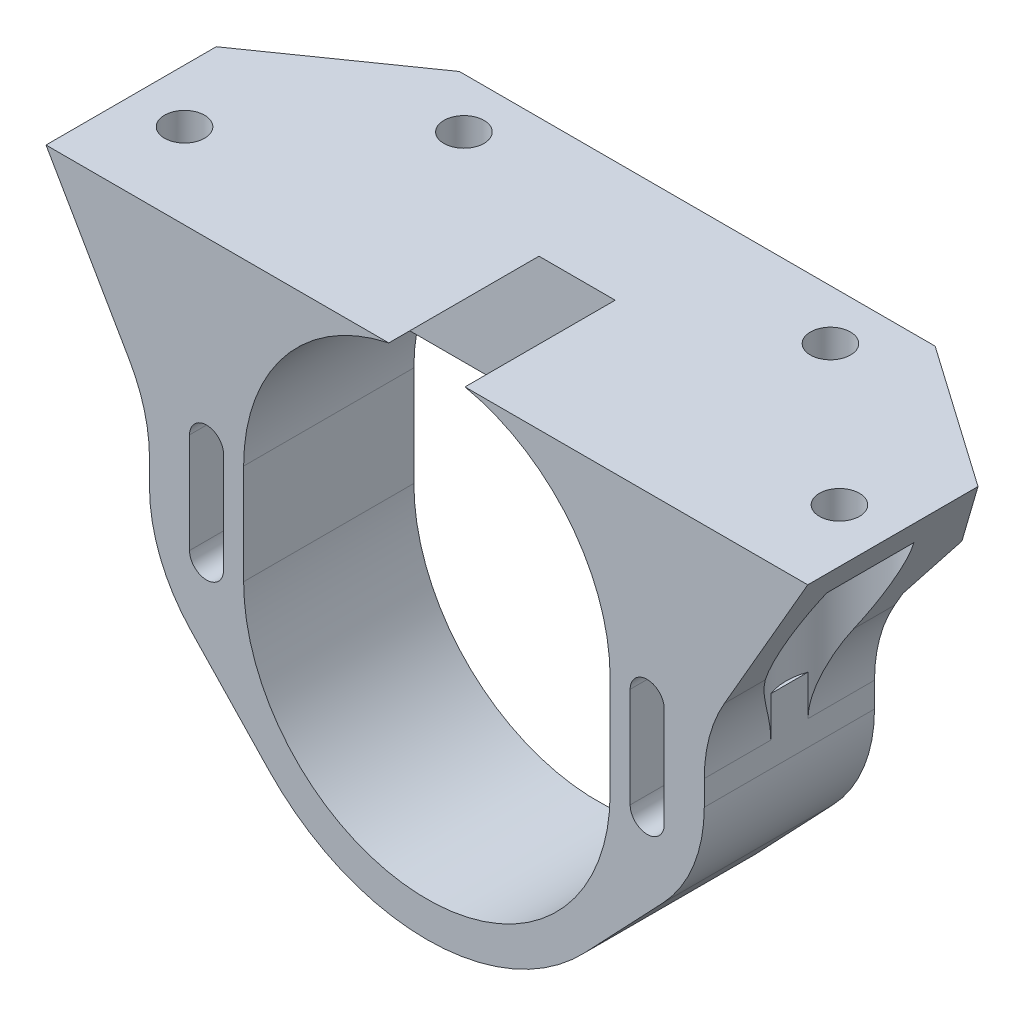
SolidWorks part; units mm, degrees
material "PA Type 6"
ref_plane "Front Plane" through (0, 0, 0) normal (0, 0, 1) x (1, 0, 0)
ref_plane "Top Plane" through (0, 0, 0) normal (0, 1, 0) x (1, 0, 0)
ref_plane "Right Plane" through (0, 0, 0) normal (1, 0, 0) x (0, 0, -1)
sketch "Sketch1" plane through (0, 0, 0) normal (0, 0, 1) x (1, 0, 0)
  line L0 (-18.3, -5) -> (-23.9501, -5) construction
  line L2 (150.8125, 17.9) -> (-150.8125, 17.9)
  line L3 (38.0346, 17.9) -> (3.8053, 17.9)
  line L4 (-15.8012, -25.0187) -> (-27.7, -12.5)
  line L5 (27.7, 0) -> (38.0346, 17.9)
  line L6 (18.3, 0) -> (18.3, -10)
  line L7 (18.3, -5) -> (23.9501, -5) construction
  line L8 (22, 0) -> (22, -10) construction
  line L9 (23.7, 0) -> (23.7, -10)
  line L10 (20.3, 0) -> (20.3, -10)
  line L11 (27.7, 0) -> (27.7, -12.5)
  line L12 (15.8012, -25.0187) -> (27.7, -12.5)
  line L13 (0, 0) -> (0, -39.0494) construction
  line L14 (-27.7, 0) -> (-27.7, -12.5)
  line L15 (-18.3, 0) -> (-18.3, -10)
  line L16 (-27.7, 0) -> (-38.0346, 17.9)
  line L17 (-38.0346, 17.9) -> (-3.8053, 17.9)
  line L18 (-22, 0) -> (-22, -10) construction
  line L19 (-23.7, 0) -> (-23.7, -10)
  line L20 (-20.3, 0) -> (-20.3, -10)
  arc A0 (18.3, 0) -> (3.8053, 17.9) centre (0, 0) ccw
  circle A1 centre (0, 0) radius 18
  circle A2 centre (0, 0) radius 18 construction
  circle A3 centre (0, 0) radius 18.3 construction
  arc A5 (-18.3, 0) -> (-3.8053, 17.9) centre (0, 0) cw
  arc A6 (18.3, -10) -> (-18.3, -10) centre (0, -10) cw
  arc A7 (15.8012, -25.0187) -> (-15.8012, -25.0187) centre (0, -10) cw
  arc A8 (21.8, -10) -> (4.533, -31.3235) centre (0, -10) cw construction
  arc A9 (23.7, 0) -> (20.3, 0) centre (22, 0) ccw
  arc A10 (20.3, -10) -> (23.7, -10) centre (22, -10) ccw
  arc A11 (18.3, -10) -> (3.8053, -27.9) centre (0, -10) cw construction
  arc A12 (-23.7, 0) -> (-20.3, 0) centre (-22, 0) cw
  arc A13 (-20.3, -10) -> (-23.7, -10) centre (-22, -10) cw
  point P19 (22, -5)
  point P41 (-22, -5)
  dimension "D7" = 1.7
  dimension "D4" = 60
  dimension "D5" = 10
  dimension "D8" = 4
  dimension "D9" = 2.5
  dimension "D10" = 10
  dimension "D1" = 0
  dimension "D2" = 0.3
  dimension "D3" = 0.1
  dimension "D6" = 3.5
extrude "Boss-Extrude1" add sketch "Sketch1" along normal offset from surface (17 mm away) 2.5 offset beyond the face yes
sketch "Sketch2" plane through (0, 0, 17) normal (0, 0, 1) x (1, 0, 0)
  line L0 (38.0346, 17.9) -> (-38.0346, 17.9)
  line L1 (-38.0346, 17.9) -> (-30.5868, 5)
  line L2 (-38.0346, 17.9) -> (-27.7, 0) construction
  line L3 (-30.5868, 5) -> (30.5868, 5)
  line L4 (27.7, 0) -> (38.0346, 17.9) construction
  line L5 (30.5868, 5) -> (38.0346, 17.9)
  dimension "D1" = 5
extrude "Boss-Extrude2" add sketch "Sketch2" along normal blind 2 from surface starting at face at (22, -5, 0)
sketch "Sketch3" plane through (0, 0, 0) normal (0, 1, 0) x (1, 0, 0)
  line L0 (38.0346, -17) -> (38.0346, 0) construction
  line L1 (27.7, -17) -> (27.7, 0) construction
  circle A0 centre (32.7, -8.5) radius 2
  point P6 (38.0346, -8.5)
  dimension "D1" = 4
  dimension "D2" = 5
extrude "Cut-Extrude2" cut sketch "Sketch3" along normal through all
sketch "Sketch4" plane through (0, 0, 0) normal (0, 1, 0) x (1, 0, 0)
  line L0 (38.0346, -17) -> (38.0346, 0) construction
  circle A0 centre (32.7, -8.5) radius 5.3346
extrude "Cut-Extrude3" cut sketch "Sketch4" along normal blind 14
sketch "Sketch5" plane through (0, 17.9, 0) normal (0, 1, 0) x (1, 0, 0)
  line L0 (-38.0346, 0) -> (-23.7531, 10)
  line L1 (-23.7531, 10) -> (0, 10)
  line L2 (0, 10) -> (0, 0)
  line L3 (38.0346, 0) -> (-38.0346, 0) construction
  line L4 (0, 0) -> (-38.0346, 0)
  circle A0 centre (-18.3, 5) radius 2
  dimension "D1" = 4
  dimension "D2" = 5
  dimension "D3" = 2
  dimension "D4" = 5
  dimension "D5" = 35
extrude "Boss-Extrude3" add sketch "Sketch5" against normal blind 3
sketch "Sketch6" plane through (0, 0, -10) normal (0, 0, -1) x (-1, 0, 0)
  line L0 (36.3025, 14.9) -> (38.0346, 17.9)
  line L1 (38.0346, 17.9) -> (38.0346, 14.9)
  line L2 (38.0346, 14.9) -> (36.3025, 14.9)
extrude "Cut-Extrude4" cut sketch "Sketch6" against normal through all
mirror "Mirror2" about plane through (0, 14.9, -10) normal (1, 0, 0) of "Cut-Extrude2", "Boss-Extrude3", "Cut-Extrude3"
mirror "Mirror3" about plane through (0, 0, 0) normal (1, 0, 0) of "Cut-Extrude3", "Cut-Extrude2", "Cut-Extrude4"
chamfer "Chamfer2" distance 10 angle 45 1 edges at (0, 14.9, 0)
sketch "Sketch7" plane through (0, 14, 0) normal (0, -1, 0) x (1, 0, 0)
  line L0 (-27.7, 0) -> (-15.8012, 0) construction
  circle A0 centre (-18.3, -5) radius 5
fillet "Fillet1" radius 15 2 edges at (27.7, -12.5, 8.5) (-27.7, -12.5, 8.5)
fillet "Fillet2" radius 15 4 edges at (27.7, 0, 13.6797) (27.7, 0, 3.3203) (-27.7, 0, 13.6797) (-27.7, 0, 3.3203)
extrude "Cut-Extrude6" cut sketch "Sketch7" along normal through all
mirror "Mirror4" about plane through (0, 0, 0) normal (1, 0, 0) of "Cut-Extrude6"
